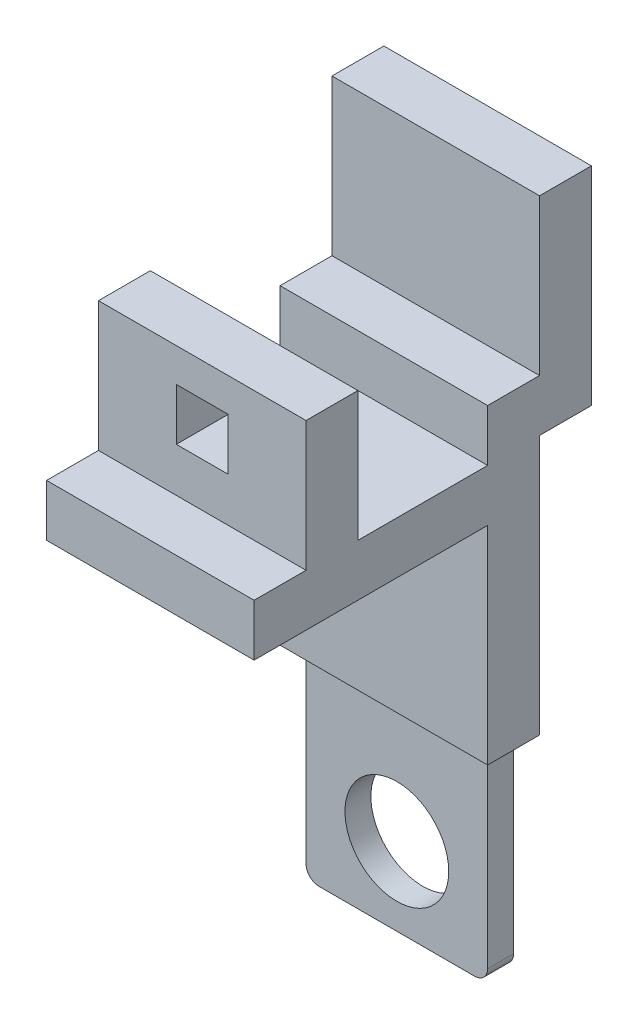
SolidWorks part; units mm, degrees
material "Czyste srebro"
ref_plane "Front Plane" through (0, 0, 0) normal (0, 0, 1) x (1, 0, 0)
ref_plane "Top Plane" through (0, 0, 0) normal (0, 1, 0) x (1, 0, 0)
ref_plane "Right Plane" through (0, 0, 0) normal (1, 0, 0) x (0, 0, -1)
sketch "Szkic1" plane through (0, 0, 0) normal (0, 1, 0) x (1, 0, 0)
  line L1 (-2, -0.5) -> (2, -0.5)
  line L2 (-2, -0.5) -> (-2, 0.5)
  line L3 (-2, 0.5) -> (2, 0.5)
  line L4 (2, -0.5) -> (2, 0.5)
  line L5 (-2, -0.5) -> (2, 0.5) construction
  line L6 (-2, 0.5) -> (2, -0.5) construction
  point P0 (0, 0)
  dimension "D1" = 4
  dimension "D2" = 1
extrude "Dodanie-wyciągnięcie1" add sketch "Szkic1" along normal blind 5 contours L3 L4 L1 L2
sketch "Szkic2" plane through (0, 0, 0.5) normal (0, 0, 1) x (1, 0, 0)
  line L0 (-2, 5) -> (-2, 0) construction
  line L1 (2, 5) -> (-2, 5)
  line L2 (2, 5) -> (2, 4)
  line L3 (2, 4) -> (-2, 4)
  line L4 (-2, 5) -> (-2, 4)
extrude "Dodanie-wyciągnięcie2" add sketch "Szkic2" along normal blind 4.5
sketch "Szkic3" plane through (0, 5, 0) normal (0, 1, 0) x (1, 0, 0)
  line L0 (2, -5) -> (2, 0.5) construction
  line L1 (-2, 0.5) -> (2, 0.5)
  line L2 (-2, 0.5) -> (-2, -0.5)
  line L3 (-2, -0.5) -> (2, -0.5)
  line L4 (2, 0.5) -> (2, -0.5)
extrude "Dodanie-wyciągnięcie3" add sketch "Szkic3" along normal blind 1
sketch "Szkic4" plane through (0, 0, -0.5) normal (0, 0, -1) x (-1, 0, 0)
  line L0 (-2, 6) -> (-2, 0) construction
  line L1 (2, 6) -> (-2, 6)
  line L2 (2, 6) -> (2, 5)
  line L3 (2, 5) -> (-2, 5)
  line L4 (-2, 6) -> (-2, 5)
extrude "Dodanie-wyciągnięcie4" add sketch "Szkic4" along normal blind 1
sketch "Szkic5" plane through (0, 6, 0) normal (0, 1, 0) x (1, 0, 0)
  line L0 (2, -0.5) -> (2, 1.5) construction
  line L1 (-2, 1.5) -> (2, 1.5)
  line L2 (-2, 1.5) -> (-2, 0.5)
  line L3 (-2, 0.5) -> (2, 0.5)
  line L4 (2, 1.5) -> (2, 0.5)
extrude "Dodanie-wyciągnięcie5" add sketch "Szkic5" along normal blind 3
sketch "Szkic6" plane through (0, 5, 0) normal (0, 1, 0) x (1, 0, 0)
  line L0 (0, -5) -> (0, -4) construction
  line L1 (2, -5) -> (-2, -5) construction
  line L2 (-2, -5) -> (-2, -0.5) construction
  line L3 (-2, -4) -> (2, -4)
  line L4 (-2, -4) -> (-2, -3)
  line L5 (-2, -3) -> (2, -3)
  line L6 (2, -4) -> (2, -3)
  line L7 (2, -5) -> (2, -0.5) construction
extrude "Dodanie-wyciągnięcie6" add sketch "Szkic6" along normal blind 2.5
sketch "Szkic8" plane through (0, 0, 0) normal (0, -1, 0) x (1, 0, 0)
  line L1 (1.75, -0.25) -> (-1.75, -0.25)
  line L2 (1.75, -0.25) -> (1.75, 0.25)
  line L3 (1.75, 0.25) -> (-1.75, 0.25)
  line L4 (-1.75, -0.25) -> (-1.75, 0.25)
  line L5 (1.75, -0.25) -> (-1.75, 0.25) construction
  line L6 (1.75, 0.25) -> (-1.75, -0.25) construction
  point P0 (0, 0)
extrude "Dodanie-wyciągnięcie7" add sketch "Szkic8" along normal blind 3.9
sketch "Szkic9" plane through (0, 0, 0.25) normal (0, 0, 1) x (1, 0, 0)
  line L0 (0, -3.9) -> (0, -2.4) construction
  line L1 (1.75, -3.9) -> (-1.75, -3.9) construction
  circle A0 centre (0, -2.4) radius 1
extrude "Wytnij-wyciągnięcie2" cut sketch "Szkic9" against normal blind 3.9
fillet "Zaokrąglenie1" radius 0.25 6 edges at (1.75, 0, 0) (0, 0, -0.25) (-1.75, 0, 0) (0, 0, 0.25) (1.75, -3.9, 0) (-1.75, -3.9, 0)
sketch "Szkic10" plane through (0, 0, 4) normal (0, 0, 1) x (1, 0, 0)
  line L0 (0, 7.5) -> (0, 6.3522) construction
  line L1 (-2, 7.5) -> (2, 7.5) construction
  line L3 (-0.5, 5.8522) -> (0.5, 5.8522)
  line L4 (-0.5, 5.8522) -> (-0.5, 6.8522)
  line L5 (-0.5, 6.8522) -> (0.5, 6.8522)
  line L6 (0.5, 5.8522) -> (0.5, 6.8522)
  line L7 (-0.5, 5.8522) -> (0.5, 6.8522) construction
  line L8 (-0.5, 6.8522) -> (0.5, 5.8522) construction
extrude "Wytnij-wyciągnięcie3" cut sketch "Szkic10" against normal blind 1
